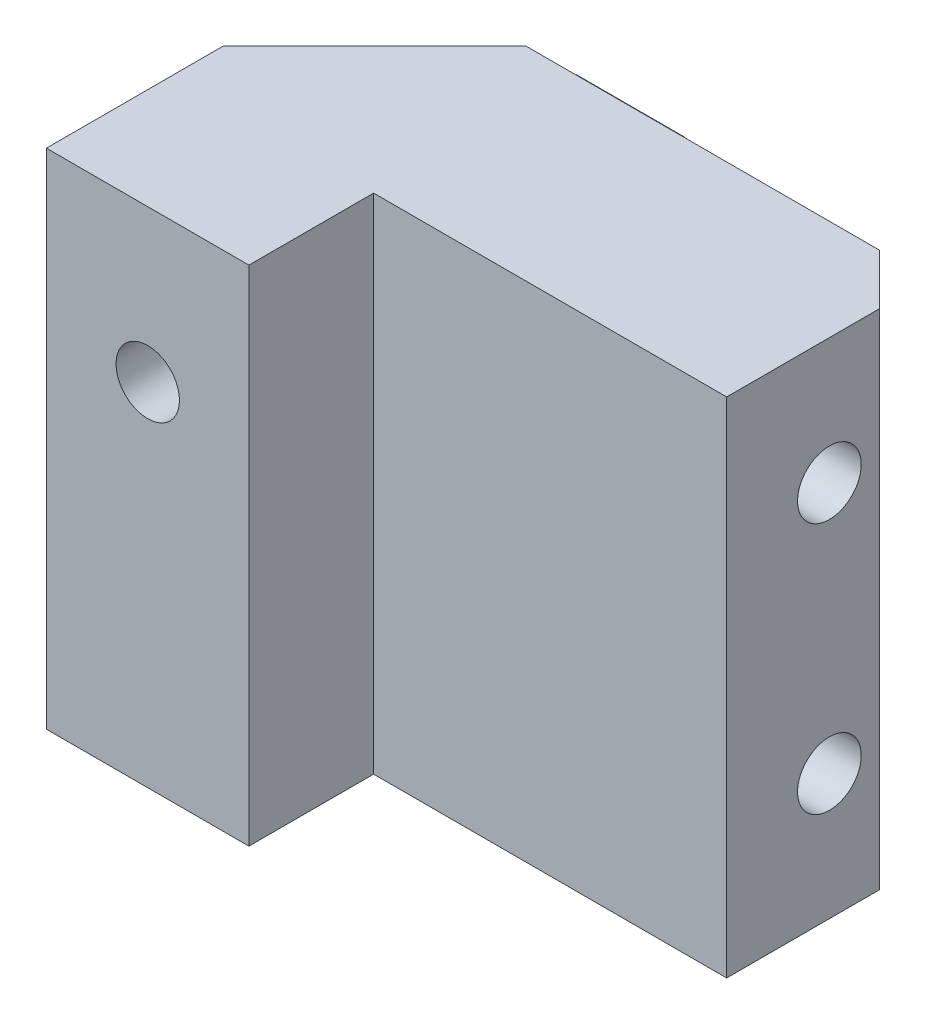
SolidWorks part; units mm, degrees
material "1060 Alloy"
ref_plane "Front Plane" through (0, 0, 0) normal (0, 0, 1) x (1, 0, 0)
ref_plane "Top Plane" through (0, 0, 0) normal (0, 1, 0) x (1, 0, 0)
ref_plane "Right Plane" through (0, 0, 0) normal (1, 0, 0) x (0, 0, -1)
sketch "Sketch1" plane through (0, 0, 0) normal (0, 1, 0) x (1, 0, 0)
  line L0 (-6.365, 0) -> (6.355, 0)
  line L1 (6.355, 0) -> (6.355, 7.83)
  line L2 (6.355, 7.83) -> (28.525, 7.83)
  line L3 (28.525, 7.83) -> (28.525, 17.435)
  line L4 (28.525, 17.435) -> (25.35, 20.61)
  line L5 (25.35, 20.61) -> (3.135, 20.61)
  line L6 (3.135, 20.61) -> (-6.365, 11.11)
  line L7 (-6.365, 11.11) -> (-6.365, 0)
  line L8 (0, 0) -> (0, 4.5392) construction
  line L9 (-2.165, 0) -> (-2.165, 1.6664) construction
  line L10 (-2.165, 1.6664) -> (2.165, 1.6664) construction
  line L11 (2.165, 1.6664) -> (2.165, 0) construction
  dimension "D1" = 12.78
  dimension "D2" = 45
  dimension "D3" = 34.89
  dimension "D4" = 12.72
  dimension "D5" = 4.2
  dimension "D6" = 4.19
  dimension "D7" = 20.61
  dimension "D8" = 9.5
  dimension "D9" = 3.175
extrude "Boss-Extrude1" add sketch "Sketch1" along normal blind 15.8 and the other way blind 15.8
sketch "Sketch2" plane through (0, 0, 0) normal (0, 0, 1) x (1, 0, 0)
  line L0 (0, 6.26) -> (0, 0) construction
  line L1 (0, 8.25) -> (-6.365, 8.25) construction
  line L2 (-6.365, -15.8) -> (-6.365, 15.8) construction
  line L3 (0, 4.27) -> (-6.365, 4.27) construction
  line L5 (-6.365, -15.8) -> (6.355, -15.8) construction
  circle A0 centre (0, 6.26) radius 1.99
  dimension "D1" = 7.55
  dimension "D2" = 20.07
extrude "Cut-Extrude1" cut sketch "Sketch2" against normal blind 6.15
sketch "Sketch3" plane through (28.525, 0, 0) normal (1, 0, 0) x (0, 0, -1)
  line L0 (14.28, -7.91) -> (14.28, 7.91) construction
  line L1 (14.28, 0) -> (0, 0) construction
  line L2 (14.28, 9.91) -> (7.83, 9.91) construction
  line L3 (7.83, -15.8) -> (7.83, 15.8) construction
  line L4 (7.83, 15.8) -> (17.435, 15.8) construction
  line L5 (12.28, 7.91) -> (12.28, 0) construction
  circle A0 centre (14.28, -7.91) radius 2
  circle A1 centre (14.28, 7.91) radius 2
  dimension "D1" = 4
  dimension "D2" = 5.89
  dimension "D3" = 4.45
extrude "Cut-Extrude2" cut sketch "Sketch3" against normal blind 16.2
sketch "Sketch4" plane through (0, 0, -20.61) normal (0, 0, -1) x (-1, 0, 0)
  line L0 (0, 0) -> (-12.25, 0) construction
  line L1 (-12.25, -15.5) -> (-5.435, -15.5)
  line L2 (-12.25, -15.5) -> (-12.25, 14.97)
  line L3 (-12.25, 14.97) -> (-5.435, 14.97)
  line L4 (-5.435, -15.5) -> (-5.435, 14.97)
  line L5 (-25.35, -15.8) -> (-25.35, 15.8) construction
  line L6 (-3.135, -15.8) -> (-3.135, 15.8) construction
  line L7 (-25.35, 15.8) -> (-3.135, 15.8) construction
  line L8 (-25.35, -15.8) -> (-3.135, -15.8) construction
  dimension "D1" = 13.1
  dimension "D2" = 2.3
  dimension "D3" = 0.83
  dimension "D4" = 0.3
extrude "Boss-Extrude2" add sketch "Sketch4" along normal blind 0.86 separate body
